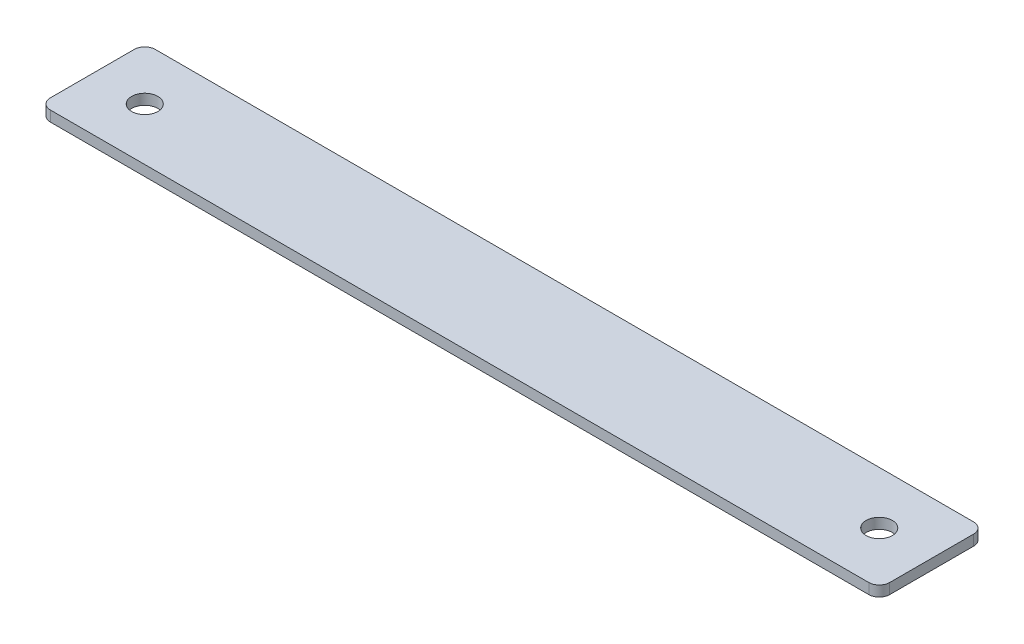
SolidWorks part; units mm, degrees
material "普通碳钢"
ref_plane "前视基准面" through (0, 0, 0) normal (0, 0, 1) x (1, 0, 0)
ref_plane "上视基准面" through (0, 0, 0) normal (0, 1, 0) x (1, 0, 0)
ref_plane "右视基准面" through (0, 0, 0) normal (1, 0, 0) x (0, 0, -1)
sketch "草图1" plane through (0, 0, 0) normal (0, 1, 0) x (1, 0, 0)
  line L0 (-154.9231, 0) -> (201.8535, 0) construction
  line L1 (0, 167.3351) -> (0, -149.0068) construction
  line L2 (-78, 10) -> (78, 10)
  line L3 (80, 8) -> (80, -8)
  line L4 (78, -10) -> (-78, -10)
  line L5 (-80, -8) -> (-80, 8)
  arc A0 (78, 10) -> (80, 8) centre (78, 8) cw
  arc A1 (80, -8) -> (78, -10) centre (78, -8) cw
  arc A2 (-78, -10) -> (-80, -8) centre (-78, -8) cw
  arc A3 (-78, 10) -> (-80, 8) centre (-78, 8) ccw
  circle A4 centre (-70, 0) radius 2.5
  circle A5 centre (70, 0) radius 2.5
  dimension "D3" = 2
  dimension "D5" = 5
  dimension "D1" = 160
  dimension "D2" = 20
  dimension "D4" = 140
base flange "基体-法兰1" sketch "草图1" thickness 2 reverse thickness direction no parameters "D1"=2
sketch "折弯-线1" [suppressed] plane through (0, 0, 0) normal (0, 1, 0) x (1, 0, 0)
sketch "边界框1" [suppressed] plane through (0, 0, 0) normal (0, 1, 0) x (1, 0, 0)
sheet metal parameters "钣金6" thickness 2 parameters "D1"=2
flat pattern "平板型式6" [suppressed]
sketch "折弯-线2" plane through (0, 0, 0) normal (0, 1, 0) x (1, 0, 0)
sketch3d "边界框2" [suppressed]
  line L0 (2, 2, 0) -> (-158, 2, 0) construction
  line L1 (2, -18, 0) -> (-158, -18, 0) construction
  line L2 (2, 2, 0) -> (2, -18, 0) construction
  line L3 (-158, 2, 0) -> (-158, -18, 0) construction
